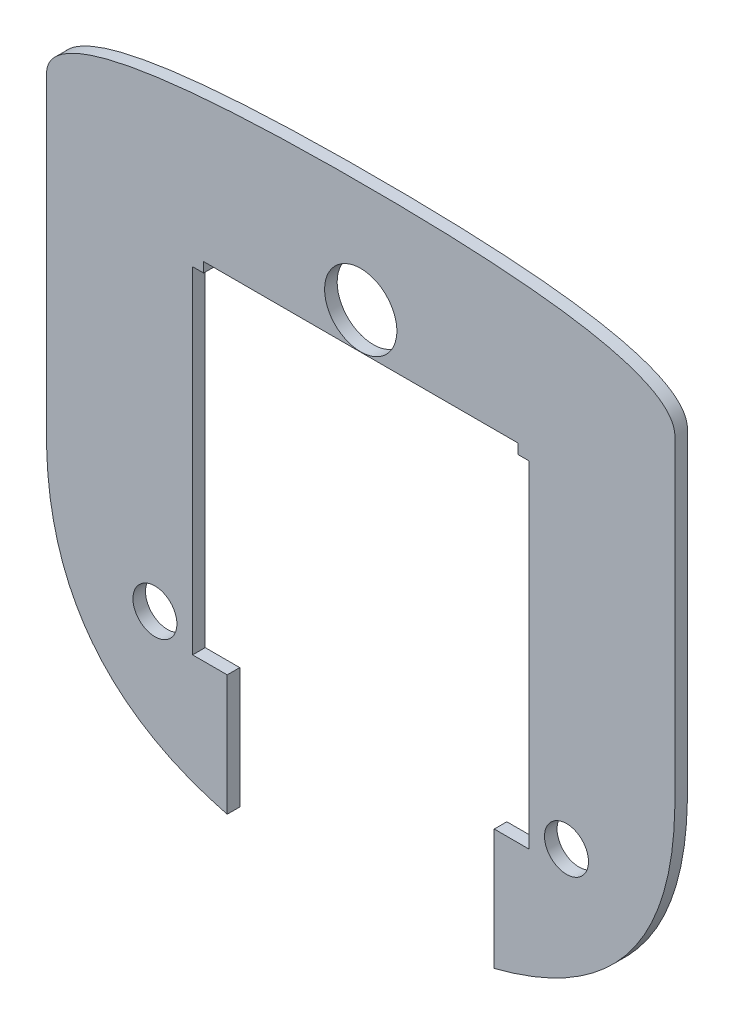
SolidWorks part; units mm, degrees
ref_plane "Front Plane" through (0, 0, 0) normal (0, 0, 1) x (1, 0, 0)
ref_plane "Top Plane" through (0, 0, 0) normal (0, 1, 0) x (1, 0, 0)
ref_plane "Right Plane" through (0, 0, 0) normal (1, 0, 0) x (0, 0, -1)
ref_plane "Plane1" through (0, 0, 650) normal (0, 0, -1) x (-1, 0, 0)
sketch "Sketch1" plane through (0, 0, 650) normal (0, 0, -1) x (-1, 0, 0)
  line L0 (0, 120) -> (0, -80) construction
  line L1 (0, 70.1122) -> (0, -75.0001) construction
  line L5 (-53.5, -36.8878) -> (-53.5, 70.1122)
  line L7 (53.5, -36.8878) -> (53.5, 70.1122)
  line L8 (-53.5, -36.8878) -> (-42.5, -36.8878)
  line L9 (-42.5, -80) -> (42.5, -80)
  line L10 (50, 73.2872) -> (-50, 73.2872) construction
  line L11 (-42.5, -36.8878) -> (-42.5, -80)
  line L12 (-50, 70.1122) -> (50, 70.1122) construction
  line L13 (50, 70.1122) -> (50, 73.2872)
  line L14 (50, 73.2872) -> (-50, 73.2872)
  line L15 (-50, 73.2872) -> (-50, 70.1122)
  line L16 (-50, 70.1122) -> (-53.5, 70.1122)
  line L18 (53.5, 70.1122) -> (50, 70.1122)
  line L19 (-42.5, -80) -> (-42.5, -36.8878) construction
  line L20 (42.5, -36.8878) -> (42.5, -80)
  line L21 (42.5, -36.8878) -> (53.5, -36.8878)
  line L22 (-42.5, -36.8878) -> (42.5, -36.8878) construction
  circle A0 centre (-65.5, -30.8878) radius 7
  circle A1 centre (65.5, -30.8878) radius 7
  circle A5 centre (0, 84.8872) radius 11.5
  spline S0 degree 3 poles (-100, 91.6667) (-100, 100.5541) (-99.8835, 101.663) (-99.344, 103.2464) (-98.4974, 104.6847) (-97.0622, 106.3843) (-94.8888, 108.1258) (-91.9976, 109.7782) (-88.9551, 111.1271) (-85.8262, 112.2552) (-82.6425, 113.2169) (-79.4227, 114.0479) (-76.1777, 114.7739) (-72.9147, 115.4129) (-69.6383, 115.979) (-65.2561, 116.6501) (-59.7591, 117.3544) (-53.1437, 118.032) (-46.5161, 118.5751) (-37.6683, 119.1501) (-26.5955, 119.6359) (-13.2992, 119.9414) (-4.4331, 120) (4.4331, 120) (13.2992, 119.9414) (26.5955, 119.6359) (37.6683, 119.1501) (46.5161, 118.5751) (53.1437, 118.032) (59.7591, 117.3544) (65.2561, 116.6501) (69.6383, 115.979) (72.9147, 115.4129) (76.1777, 114.7739) (79.4227, 114.0479) (82.6425, 113.2169) (85.8262, 112.2552) (88.9551, 111.1271) (91.9976, 109.7782) (94.8888, 108.1258) (97.0622, 106.3843) (98.4974, 104.6847) (99.344, 103.2464) (99.8835, 101.663) (100, 100.5541) (100, 91.6667) (100, 75) (100, 50) (100, 25) (100, 8.3333) (100, -3.0509) (99.7823, -9.1535) (98.6814, -18.2496) (96.6708, -27.1928) (93.6177, -35.841) (89.4261, -44.0037) (84.0794, -51.4648) (77.6729, -58.0369) (70.3884, -63.6161) (62.4486, -68.1997) (51.2385, -73.0758) (36.4788, -77.1218) (18.3084, -79.5568) (6.1019, -80) (-6.1019, -80) (-18.3084, -79.5568) (-36.4788, -77.1218) (-51.2385, -73.0758) (-62.4486, -68.1997) (-70.3884, -63.6161) (-77.6729, -58.0369) (-84.0794, -51.4648) (-89.4261, -44.0037) (-93.6177, -35.841) (-96.6708, -27.1928) (-98.6814, -18.2496) (-99.7823, -9.1535) (-100, -3.0509) (-100, 8.3333) (-100, 25) (-100, 50) (-100, 75) (-100, 91.6667) (-100, 100.5541) (-99.8835, 101.663) knots -0.070853 -0.035426 0 0 0.002356 0.004712 0.007067 0.009423 0.014135 0.018847 0.023558 0.02827 0.032982 0.037693 0.042405 0.047116 0.051828 0.05654 0.065963 0.075386 0.08481 0.094233 0.11308 0.131926 0.150773 0.150773 0.169619 0.188466 0.207313 0.216736 0.226159 0.235583 0.245006 0.249718 0.254429 0.259141 0.263853 0.268564 0.273276 0.277988 0.282699 0.287411 0.292123 0.294478 0.296834 0.29919 0.301546 0.301546 0.336972 0.372399 0.407825 0.443252 0.443252 0.456222 0.469192 0.482162 0.495132 0.508102 0.521072 0.534042 0.547012 0.559982 0.572952 0.598893 0.624833 0.650773 0.650773 0.676713 0.702653 0.728593 0.741563 0.754533 0.767504 0.780474 0.793444 0.806414 0.819384 0.832354 0.845324 0.858294 0.858294 0.893721 0.929147 0.964574 1 1 1.002356 1.004712 1.007067 only from (-100, 100) to (-100, 100)
  spline S1 degree 3 poles (-100, 91.6667) (-100, 100.5541) (-99.8835, 101.663) (-99.344, 103.2464) (-98.4974, 104.6847) (-97.0622, 106.3843) (-94.8888, 108.1258) (-91.9976, 109.7782) (-88.9551, 111.1271) (-85.8262, 112.2552) (-82.6425, 113.2169) (-79.4227, 114.0479) (-76.1777, 114.7739) (-72.9147, 115.4129) (-69.6383, 115.979) (-65.2561, 116.6501) (-59.7591, 117.3544) (-53.1437, 118.032) (-46.5161, 118.5751) (-37.6683, 119.1501) (-26.5955, 119.6359) (-13.2992, 119.9414) (-4.4331, 120) (4.4331, 120) (13.2992, 119.9414) (26.5955, 119.6359) (37.6683, 119.1501) (46.5161, 118.5751) (53.1437, 118.032) (59.7591, 117.3544) (65.2561, 116.6501) (69.6383, 115.979) (72.9147, 115.4129) (76.1777, 114.7739) (79.4227, 114.0479) (82.6425, 113.2169) (85.8262, 112.2552) (88.9551, 111.1271) (91.9976, 109.7782) (94.8888, 108.1258) (97.0622, 106.3843) (98.4974, 104.6847) (99.344, 103.2464) (99.8835, 101.663) (100, 100.5541) (100, 91.6667) (100, 75) (100, 50) (100, 25) (100, 8.3333) (100, -3.0509) (99.7823, -9.1535) (98.6814, -18.2496) (96.6708, -27.1928) (93.6177, -35.841) (89.4261, -44.0037) (84.0794, -51.4648) (77.6729, -58.0369) (70.3884, -63.6161) (62.4486, -68.1997) (51.2385, -73.0758) (36.4788, -77.1218) (18.3084, -79.5568) (6.1019, -80) (-6.1019, -80) (-18.3084, -79.5568) (-36.4788, -77.1218) (-51.2385, -73.0758) (-62.4486, -68.1997) (-70.3884, -63.6161) (-77.6729, -58.0369) (-84.0794, -51.4648) (-89.4261, -44.0037) (-93.6177, -35.841) (-96.6708, -27.1928) (-98.6814, -18.2496) (-99.7823, -9.1535) (-100, -3.0509) (-100, 8.3333) (-100, 25) (-100, 50) (-100, 75) (-100, 91.6667) (-100, 100.5541) (-99.8835, 101.663) knots -0.070853 -0.035426 0 0 0.002356 0.004712 0.007067 0.009423 0.014135 0.018847 0.023558 0.02827 0.032982 0.037693 0.042405 0.047116 0.051828 0.05654 0.065963 0.075386 0.08481 0.094233 0.11308 0.131926 0.150773 0.150773 0.169619 0.188466 0.207313 0.216736 0.226159 0.235583 0.245006 0.249718 0.254429 0.259141 0.263853 0.268564 0.273276 0.277988 0.282699 0.287411 0.292123 0.294478 0.296834 0.29919 0.301546 0.301546 0.336972 0.372399 0.407825 0.443252 0.443252 0.456222 0.469192 0.482162 0.495132 0.508102 0.521072 0.534042 0.547012 0.559982 0.572952 0.598893 0.624833 0.650773 0.650773 0.676713 0.702653 0.728593 0.741563 0.754533 0.767504 0.780474 0.793444 0.806414 0.819384 0.832354 0.845324 0.858294 0.858294 0.893721 0.929147 0.964574 1 1 1.002356 1.004712 1.007067 only from (-100, 100) to (-100, 100)
  point P13 (0, 19.05)
  point P24 (0, 73.3872)
  point P27 (0, -80)
  dimension "D1" = 14
  dimension "D2" = 23
  dimension "D3" = 0.1
  dimension "D4" = 19.05
  dimension "D5" = 107
  dimension "D6" = 107
  dimension "D7" = 107
  dimension "D8" = 85
  dimension "D10" = 53.5
extrude "Boss-Extrude1" add sketch "Sketch1" against normal blind 4 contours S1 L11 L8 L5 L16 L15 L14 L13 L18 L7 L21 L20 A5 A0 A1 region at (48, -39.6833, 650)
